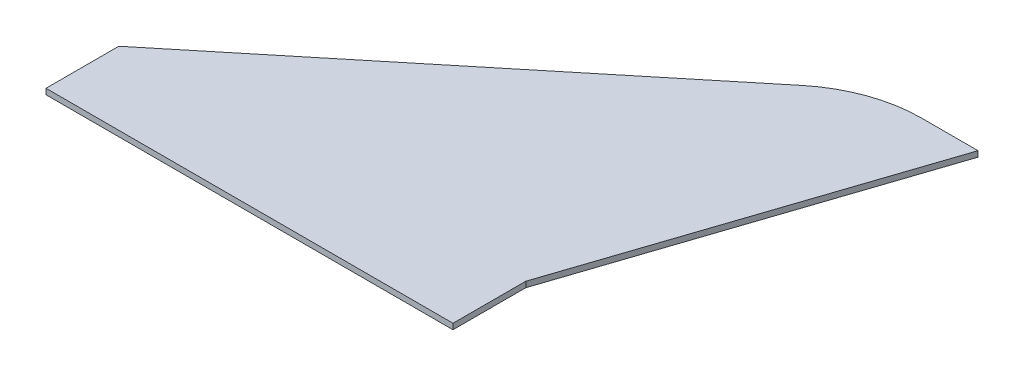
SolidWorks part; units mm, degrees
ref_plane "Front Plane" through (0, 0, 0) normal (0, 0, 1) x (1, 0, 0)
ref_plane "Top Plane" through (0, 0, 0) normal (0, 1, 0) x (1, 0, 0)
ref_plane "Right Plane" through (0, 0, 0) normal (1, 0, 0) x (0, 0, -1)
sketch "Sketch1" plane through (0, 0, 0) normal (0, 1, 0) x (1, 0, 0)
  line L0 (0, 40.894) -> (210.82, 213.614)
  line L1 (0, 0) -> (228.6, 0)
  line L2 (0, 0) -> (0, 40.894)
  line L4 (228.6, 0) -> (228.6, 40.894)
  line L6 (292.1, 231.394) -> (228.6, 40.894)
  line L7 (292.1, 231.394) -> (260.5775, 231.394)
  line L8 (0, 40.894) -> (228.6, 40.894) construction
  arc A0 (260.5775, 231.394) -> (210.82, 213.614) centre (260.5775, 152.8806) ccw
  point P8 (0, 0)
  dimension "D1" = 228.6
  dimension "D2" = 172.72
  dimension "D3" = 190.5
  dimension "D4" = 210.82
  dimension "D5" = 292.1
  dimension "D6" = 40.894
extrude "Boss-Extrude1" add sketch "Sketch1" along normal blind 3.175 contours L1 L4 L2 | L6 L0 region at (158.5332, 0, -92.5397)
